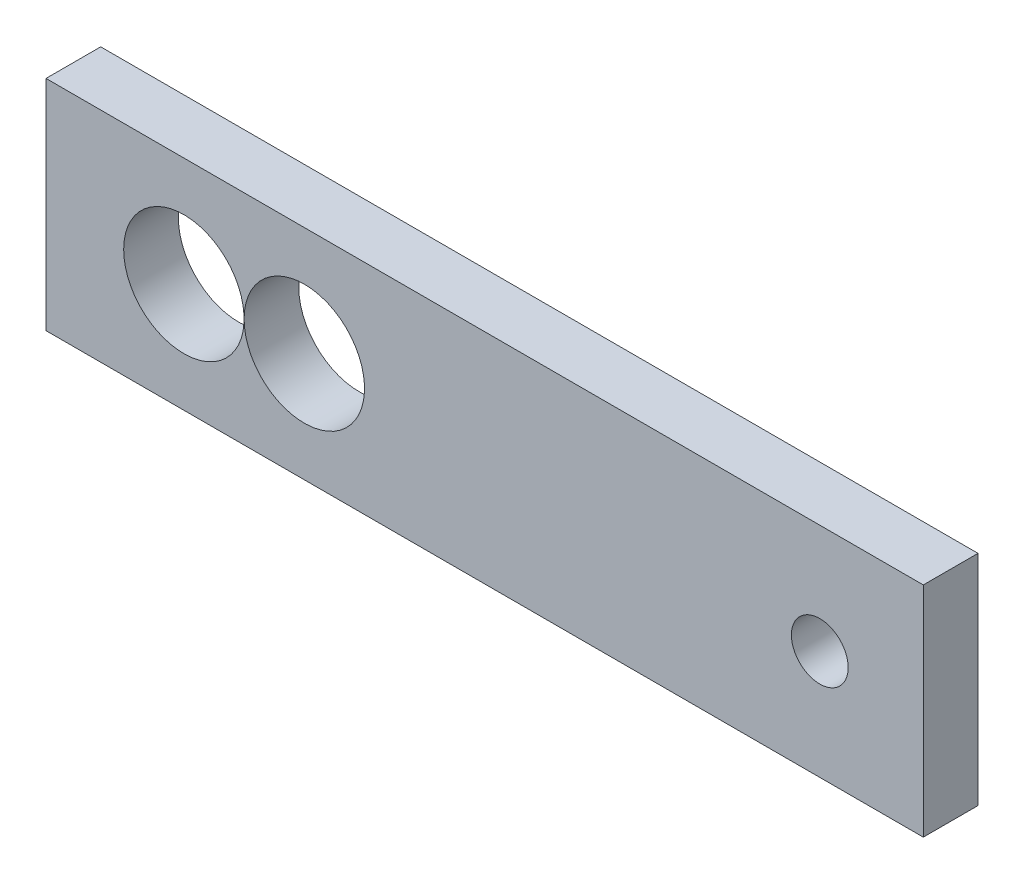
SolidWorks part; units mm, degrees
material "Cobre"
ref_plane "Plano frontal" through (0, 0, 0) normal (0, 0, 1) x (1, 0, 0)
ref_plane "Plano superior" through (0, 0, 0) normal (0, 1, 0) x (1, 0, 0)
ref_plane "Plano direito" through (0, 0, 0) normal (1, 0, 0) x (0, 0, -1)
sketch "Esboço1" plane through (0, 0, 0) normal (0, 0, 1) x (1, 0, 0)
  line L1 (25.5, 6.35) -> (-25.5, 6.35)
  line L2 (25.5, 6.35) -> (25.5, -6.35)
  line L3 (25.5, -6.35) -> (-25.5, -6.35)
  line L4 (-25.5, 6.35) -> (-25.5, -6.35)
  line L5 (25.5, 6.35) -> (-25.5, -6.35) construction
  line L6 (25.5, -6.35) -> (-25.5, 6.35) construction
  point P0 (0, 0)
  dimension "D1" = 51
  dimension "D2" = 12.7
base flange "Flange-base1" sketch "Esboço1" thickness 3.18 reverse thickness direction no parameters "D1"=0.7366
sketch "Esboço2" plane through (0, 0, -3.18) normal (0, 0, -1) x (-1, 0, 0)
  line L0 (-25.5, 6.35) -> (-13.465, -6.35) construction
  line L1 (25.5, -6.35) -> (-25.5, -6.35) construction
  line L2 (-13.465, 42.4923) -> (-13.465, -42.5077) construction
  line L3 (17.485, 0) -> (10.484, 0) construction
  circle A0 centre (17.485, 0) radius 3.5
  circle A1 centre (-19.4825, 0) radius 1.65
  circle A3 centre (10.484, 0) radius 3.5
  dimension "D1" = 7
  dimension "D2" = 3.3
  dimension "D4" = 7.001
  dimension "D3" = 7
extrude "Corte-extrusão1" cut sketch "Esboço2" against normal blind 10 normal cut yes
sketch "Curva-Linhas1" [suppressed] plane through (0, 0, 0) normal (0, 1, 0) x (1, 0, 0)
sketch "Caixa delimitadora1" [suppressed] plane through (0, 0, 0) normal (0, 1, 0) x (1, 0, 0)
sheet metal parameters "Chapa metálica1" thickness 3.18 parameters "D1"=0.7366
flat pattern "Padrão-Plano1" [suppressed]
sketch "Curva-Linhas2" plane through (0, 0, 0) normal (0, 0, 1) x (1, 0, 0)
sketch3d "Caixa delimitadora2" [suppressed]
  line L0 (-25.5, -6.35, 0) -> (25.5, -6.35, 0) construction
  line L1 (-25.5, 6.35, 0) -> (25.5, 6.35, 0) construction
  line L2 (-25.5, -6.35, 0) -> (-25.5, 6.35, 0) construction
  line L3 (25.5, -6.35, 0) -> (25.5, 6.35, 0) construction
sheet metal parameters "Chapa metálica2" thickness 3.18 parameters "D1"=0.7366
flat pattern "Padrão-Plano1"
sketch "Curva-Linhas2" plane through (0, 0, 0) normal (0, 0, 1) x (1, 0, 0)
sketch3d "Caixa delimitadora2" [suppressed]
  line L0 (-25.5, -6.35, 0) -> (25.5, -6.35, 0) construction
  line L1 (-25.5, 6.35, 0) -> (25.5, 6.35, 0) construction
  line L2 (-25.5, -6.35, 0) -> (-25.5, 6.35, 0) construction
  line L3 (25.5, -6.35, 0) -> (25.5, 6.35, 0) construction
